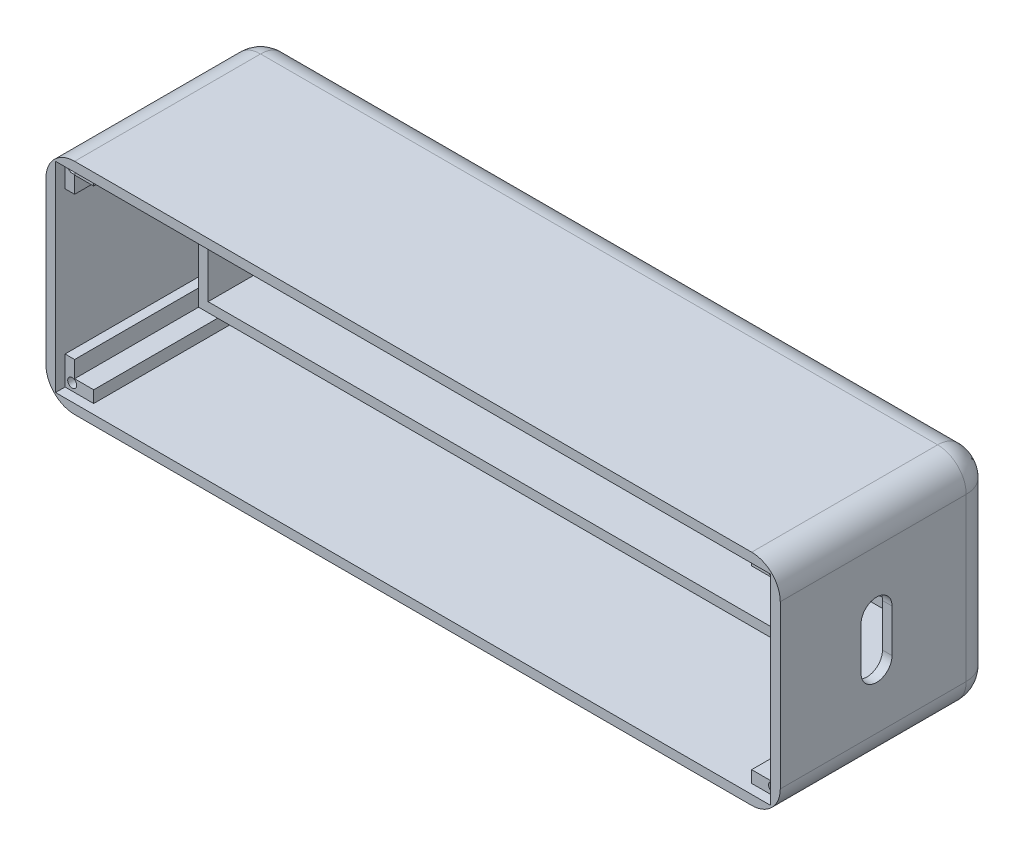
SolidWorks part; units mm, degrees
ref_plane "前视基准面" through (0, 0, 0) normal (0, 0, 1) x (1, 0, 0)
ref_plane "上视基准面" through (0, 0, 0) normal (0, 1, 0) x (1, 0, 0)
ref_plane "右视基准面" through (0, 0, 0) normal (1, 0, 0) x (0, 0, -1)
sketch "草图1" plane through (0, 0, 0) normal (0, 0, 1) x (1, 0, 0)
  line L1 (-73.7576, 4.4248) -> (76.2424, 4.4248)
  line L2 (-73.7576, 4.4248) -> (-73.7576, -37.5752)
  line L3 (-73.7576, -37.5752) -> (76.2424, -37.5752)
  line L4 (76.2424, 4.4248) -> (76.2424, -37.5752)
  line L9 (-75.7576, 6.4248) -> (78.2424, 6.4248)
  line L10 (-75.7576, 6.4248) -> (-75.7576, -39.5752)
  line L11 (-75.7576, -39.5752) -> (78.2424, -39.5752)
  line L12 (78.2424, 6.4248) -> (78.2424, -39.5752)
  dimension "D1" = 150
  dimension "D2" = 42
  dimension "D3" = 2
  dimension "D4" = 2
  dimension "D5" = 2
  dimension "D6" = 2
extrude "凸台-拉伸1" add sketch "草图1" along normal blind 43
sketch "草图2" plane through (0, 0, 0) normal (0, 0, -1) x (-1, 0, 0)
  line L1 (-78.2424, 6.4248) -> (75.7576, 6.4248)
  line L2 (-78.2424, 6.4248) -> (-78.2424, -39.5752)
  line L3 (-78.2424, -39.5752) -> (75.7576, -39.5752)
  line L4 (75.7576, 6.4248) -> (75.7576, -39.5752)
extrude "凸台-拉伸2" add sketch "草图2" along normal blind 2
sketch "草图3" plane through (0, 0, 0) normal (0, 0, 1) x (1, 0, 0)
  line L0 (76.2424, 4.4248) -> (-73.7576, 4.4248) construction
  line L1 (-69.7576, -0.0752) -> (72.2424, -0.0752)
  line L2 (-69.7576, -0.0752) -> (-69.7576, -33.0752)
  line L3 (-69.7576, -33.0752) -> (72.2424, -33.0752)
  line L4 (72.2424, -0.0752) -> (72.2424, -33.0752)
  line L5 (-73.7576, -37.5752) -> (76.2424, -37.5752) construction
  line L6 (76.2424, -37.5752) -> (76.2424, 4.4248) construction
  line L7 (-73.7576, 4.4248) -> (-73.7576, -37.5752) construction
  line L9 (-67.2249, -2.0752) -> (70.2424, -2.0752)
  line L10 (-67.2249, -2.0752) -> (-67.2249, -31.0752)
  line L11 (-67.2249, -31.0752) -> (70.2424, -31.0752)
  line L12 (70.2424, -2.0752) -> (70.2424, -31.0752)
  line L13 (-71.7576, 1.9248) -> (74.2424, 1.9248)
  line L14 (-71.7576, 1.9248) -> (-71.7576, -35.0752)
  line L15 (-71.7576, -35.0752) -> (74.2424, -35.0752)
  line L16 (74.2424, 1.9248) -> (74.2424, -35.0752)
  dimension "D1" = 142
  dimension "D2" = 33
  dimension "D3" = 4.5
  dimension "D4" = 4.5
  dimension "D5" = 4
  dimension "D6" = 4
  dimension "D7" = 2
  dimension "D8" = 2
  dimension "D9" = 2
  dimension "D10" = 2
  dimension "D11" = 2
  dimension "D12" = 2
  dimension "D13" = 2
extrude "切除-拉伸1" cut sketch "草图3" against normal blind 2 contours L10 L9 L12 L11
extrude "凸台-拉伸3" add sketch "草图3<4>" along normal blind 15 contours L16 L13 L14 L15 L1 L4 L3 L2 region at (1.2424, 0.4187, 0)
sketch "草图3<4>" plane through (0, 0, 0) normal (0, 0, 1) x (1, 0, 0) same geometry as "草图3"
sketch "草图7" plane through (0, 0, 0) normal (0, 0, 1) x (1, 0, 0)
  line L0 (-73.7576, 4.4248) -> (-67.7576, 4.4248)
  line L1 (76.2424, 4.4248) -> (-73.7576, 4.4248) construction
  line L2 (-67.7576, 4.4248) -> (-67.7576, 1.9248)
  line L3 (-71.7576, 1.9248) -> (74.2424, 1.9248) construction
  line L4 (-67.7576, 1.9248) -> (-71.7576, 1.9248)
  line L5 (-71.7576, 1.9248) -> (-71.7576, -1.5752)
  line L6 (-71.7576, 1.9248) -> (-71.7576, -35.0752) construction
  line L7 (-71.7576, -1.5752) -> (-73.7576, -1.5752)
  line L8 (-73.7576, 4.4248) -> (-73.7576, -37.5752) construction
  line L9 (-73.7576, -1.5752) -> (-73.7576, 4.4248)
  line L10 (1.2424, 4.4248) -> (1.2424, -37.5752) construction
  line L11 (-73.7576, -37.5752) -> (76.2424, -37.5752) construction
  line L12 (74.2424, -1.5752) -> (76.2424, -1.5752)
  line L13 (74.2424, 1.9248) -> (74.2424, -1.5752)
  line L14 (70.2424, 1.9248) -> (74.2424, 1.9248)
  line L15 (70.2424, 4.4248) -> (70.2424, 1.9248)
  line L16 (76.2424, 4.4248) -> (70.2424, 4.4248)
  line L17 (76.2424, -1.5752) -> (76.2424, 4.4248)
  line L18 (-73.7576, -16.5752) -> (76.2424, -16.5752) construction
  line L19 (76.2424, -37.5752) -> (76.2424, 4.4248) construction
  line L20 (74.2424, -35.0752) -> (74.2424, -31.5752)
  line L21 (70.2424, -35.0752) -> (74.2424, -35.0752)
  line L22 (70.2424, -37.5752) -> (70.2424, -35.0752)
  line L23 (76.2424, -37.5752) -> (70.2424, -37.5752)
  line L24 (76.2424, -31.5752) -> (76.2424, -37.5752)
  line L25 (74.2424, -31.5752) -> (76.2424, -31.5752)
  line L26 (-71.7576, -31.5752) -> (-73.7576, -31.5752)
  line L27 (-71.7576, -35.0752) -> (-71.7576, -31.5752)
  line L28 (-67.7576, -35.0752) -> (-71.7576, -35.0752)
  line L29 (-67.7576, -37.5752) -> (-67.7576, -35.0752)
  line L30 (-73.7576, -37.5752) -> (-67.7576, -37.5752)
  line L31 (-73.7576, -31.5752) -> (-73.7576, -37.5752)
  dimension "D1" = 2.5
  dimension "D2" = 2
  dimension "D3" = 6
  dimension "D4" = 6
extrude "凸台-拉伸9" add sketch "草图7" along normal blind 41
sketch "草图8" plane through (0, 0, 41) normal (0, 0, 1) x (1, 0, 0)
  line L0 (76.2424, 4.4248) -> (-73.7576, 4.4248) construction
  line L1 (-73.7576, 4.4248) -> (-73.7576, -1.5752) construction
  line L2 (-73.7576, -37.5752) -> (-67.7576, -37.5752) construction
  line L3 (-73.7576, -31.5752) -> (-73.7576, -37.5752) construction
  line L4 (76.2424, -37.5752) -> (76.2424, -31.5752) construction
  line L6 (70.2424, -37.5752) -> (76.2424, -37.5752) construction
  line L7 (76.2424, 4.4248) -> (70.2424, 4.4248) construction
  line L8 (76.2424, -1.5752) -> (76.2424, 4.4248) construction
  circle A0 centre (-72.2576, 2.9248) radius 0.95
  circle A1 centre (-72.2576, -36.0752) radius 0.95
  circle A2 centre (74.7424, -36.0752) radius 0.95
  circle A3 centre (74.7424, 2.9248) radius 0.95
  point P16 (-73.5883, -35.4216)
  point P21 (74.8922, -37.5752)
  point P22 (75.0116, -36.9555)
  dimension "D1" = 1.9
  dimension "D4" = 1.9
  dimension "D7" = 1.9
  dimension "D10" = 1.9
  dimension "D2" = 1.5
  dimension "D3" = 1.5
  dimension "D5" = 1.5
  dimension "D6" = 1.5
  dimension "D8" = 1.5
  dimension "D9" = 1.5
  dimension "D11" = 1.5
  dimension "D12" = 1.5
extrude "切除-拉伸2" cut sketch "草图8" against normal blind 41
fillet "圆角2" radius 6 4 edges at (78.2424, -39.5752, 20.5) (78.2424, 6.4248, 20.5) (-75.7576, -39.5752, 20.5) (-75.7576, 6.4248, 20.5)
fillet "圆角3" radius 6 8 edges at (76.485, 4.6675, -2) (1.2424, 6.4248, -2) (-74.0003, 4.6675, -2) (-75.7576, -16.5752, -2) (-74.0003, -37.8178, -2) (1.2424, -39.5752, -2) (76.485, -37.8178, -2) (78.2424, -16.5752, -2)
sketch "草图12" plane through (76.2424, 0, 0) normal (-1, 0, 0) x (0, 0, 1)
  line L0 (22.8117, -12.0752) -> (22.8117, -21.0752) construction
  line L1 (26.0617, -12.0752) -> (26.0617, -21.0752)
  line L2 (19.5617, -12.0752) -> (19.5617, -21.0752)
  line L4 (15, -33.0752) -> (0, -33.0752) construction
  line L5 (15, -0.0752) -> (0, -0.0752) construction
  arc A0 (26.0617, -12.0752) -> (19.5617, -12.0752) centre (22.8117, -12.0752) ccw
  arc A1 (19.5617, -21.0752) -> (26.0617, -21.0752) centre (22.8117, -21.0752) ccw
  point P2 (22.8117, -16.5752)
  dimension "D1" = 9
  dimension "D2" = 12
  dimension "D3" = 12
  dimension "D4" = 6.5
extrude "切除-拉伸3" cut sketch "草图12" against normal blind 41
